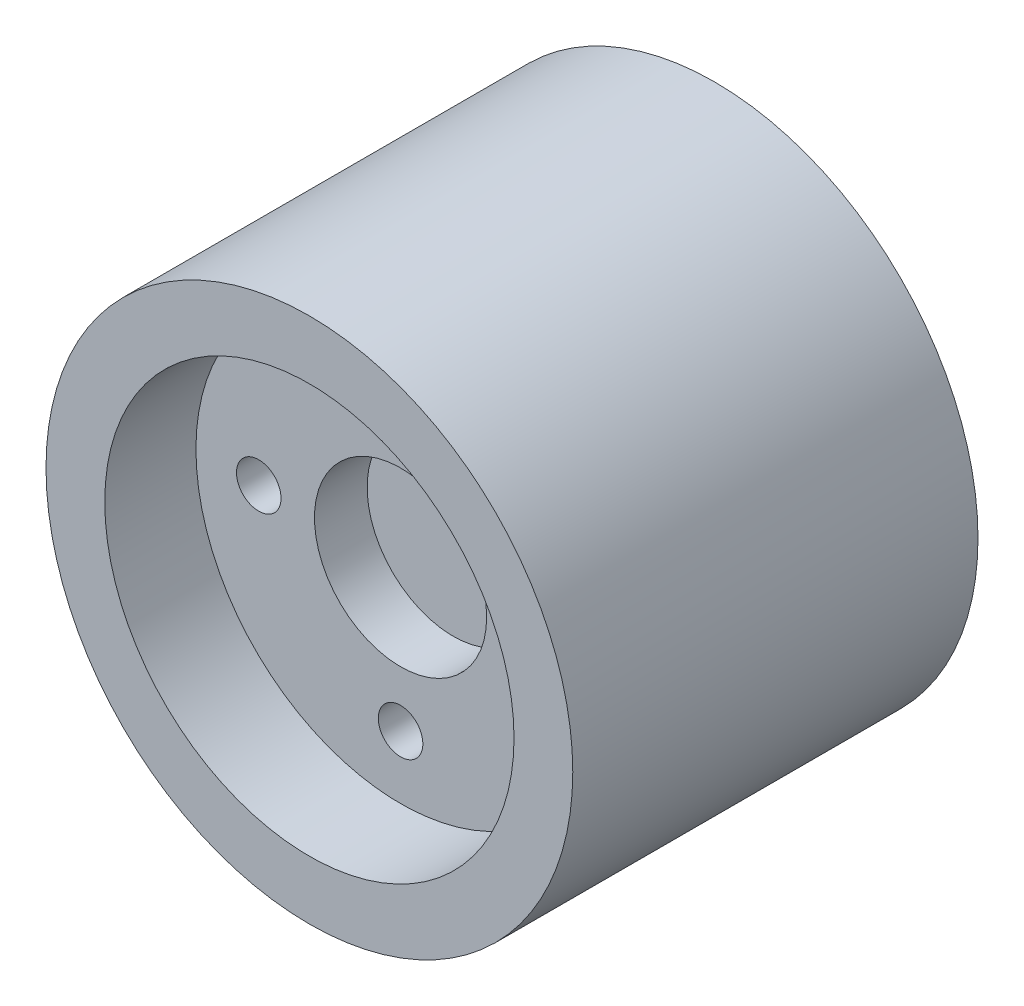
SolidWorks part; units mm, degrees
ref_plane "Front Plane" through (0, 0, 0) normal (0, 0, 1) x (1, 0, 0)
ref_plane "Top Plane" through (0, 0, 0) normal (0, 1, 0) x (1, 0, 0)
ref_plane "Right Plane" through (0, 0, 0) normal (1, 0, 0) x (0, 0, -1)
sketch "Sketch1" plane through (0, 0, 0) normal (0, 0, 1) x (1, 0, 0)
  circle A0 centre (0, 0) radius 13
  dimension "D1" = 26
extrude "Boss-Extrude1" add sketch "Sketch1" along normal blind 20
sketch "Sketch2" plane through (0, 0, 20) normal (0, 0, 1) x (1, 0, 0)
  circle A0 centre (0, 0) radius 10.1
  dimension "D1" = 20.2
extrude "Cut-Extrude1" cut sketch "Sketch2" against normal blind 4.5
sketch "Sketch3" plane through (0, 0, 15.5) normal (0, 0, 1) x (1, 0, 0)
  circle A0 centre (0, 0) radius 4.25
  dimension "D1" = 8.5
extrude "Cut-Extrude2" cut sketch "Sketch3" against normal blind 2.6
sketch "Sketch4" plane through (0, 0, 0) normal (0, 0, -1) x (-1, 0, 0)
  circle A0 centre (0, 0) radius 2.125
  dimension "D1" = 4.25
extrude "Cut-Extrude3" cut sketch "Sketch4" against normal blind 10
sketch "Sketch5" plane through (0, 0, 0) normal (0, 0, -1) x (-1, 0, 0)
  circle A0 centre (0, 7) radius 2
  circle A1 centre (7, 0) radius 2
  circle A2 centre (0, -7) radius 2
  circle A4 centre (-7, 0) radius 2 [skipped]
  circle A5 centre (0, 0) radius 2.125 construction
  point P11 (0, 0)
  dimension "D2" = 4
  dimension "D1" = 7
  dimension "D4" = 7
extrude "Cut-Extrude4" cut sketch "Sketch5" against normal offset from surface (13.5 mm away) 2 up to face at (4.25, 0, 15.5)
sketch "Sketch6" plane through (0, 0, 0) normal (0, 0, -1) x (-1, 0, 0)
  circle A0 centre (0, 7) radius 1.1
  circle A1 centre (7, 0) radius 1.1
  circle A2 centre (0, -7) radius 1.1
  circle A4 centre (-7, 0) radius 1.1 [skipped]
  circle A5 centre (0, 7) radius 2 construction
  point P12 (0, 0)
  dimension "D1" = 2.2
  dimension "D2" = 7
  dimension "D4" = 7
extrude "Cut-Extrude5" cut sketch "Sketch6" against normal through all
sketch "Sketch7" plane through (0, 0, 0) normal (0, 0, -1) x (-1, 0, 0)
  line L0 (0, 0) -> (-20.2439, 0) construction
  circle A0 centre (-6, 5) radius 2.1
  circle A1 centre (-6, -5) radius 2.1
  dimension "D3" = 4.2
  dimension "D1" = 5
  dimension "D2" = 6
extrude "Cut-Extrude6" cut sketch "Sketch7" against normal blind 6
equation "\"L1\"= 120mm'Upper arm"
equation "\"L3\"= 75mm'Wrist→TCP"
equation "\"h0\"= 75mm'Shoulder height"
equation "\"t_link\"= 3mm'Link plate thickness"
equation "\"t_bracket\"= 4mm'Bracket thickness"
equation "\"d_pin\"= 4mm'Pin diameter (M4)"
equation "\"c_fit\"= 0.2mm'Nominal clearance - measured PLA 2026-10-01"
equation "\"L2\"= 120mm'Forearm"
equation "\"c_fit_pivot\"= \"c_fit\" + 0.05mm'Gripper pivot clearance - chosen 0.25 mm 2026-10-01"
equation "\"d_pin_gripper\"= 3mm'Gripper pivot diameter"
equation "\"w_link\"= 20mm'Link plate depth (bending direction)"
equation "\"w_gap\"= 20mm'Twin-plate gap - provisional, set by elbow servo mount"
equation "\"d_boss\"= 13mm'MG996R output boss dia - from downloaded model, verify with calipers"
equation "\"c_boss\"= 1mm'Radial clearance around servo boss"
equation "\"d_servo_hole\"= \"d_boss\" + 2 * \"c_boss\"'Plate clearance hole for servo boss (15 mm)"
equation "\"t_rim\"= 9.5mm'Min material around servo hole (M3 hole + 3 mm webs each side)"
equation "\"w_link_end\"= \"d_servo_hole\" + 2 * \"t_rim\"'Link plate end width at servo end (34 mm)"
equation "\"d_hole_m3\"= \"d_pin_gripper\" + \"c_fit\"'M3 bolt clearance hole (spacer and adapter bolts)"
equation "\"d_hole_pivot\"= \"d_pin\" + \"c_fit_pivot\"'M4 pivot hole where the pin rotates (4.25 mm)"
equation "\"d_horn\"= 20mm'Horn disc diameter (circular horn) - from MG996R model"
equation "\"t_horn\"= 2.3mm'Horn disc thickness"
equation "\"g_horn\"= 2.2mm'Gap from horn disc to plate 2 inner face - from MockShoulder"
equation "\"d_horn_pocket\"= \"d_horn\" + \"c_fit\"'Adapter pocket for horn disc (20.2 mm)"
equation "\"h_horn_pocket\"= \"g_horn\" + \"t_horn\"'Pocket depth from adapter plate-2 face (4.5 mm)"
equation "\"d_horn_screw_cb\"= 8.5mm'Recess for horn centre-screw head (head is 7.5 mm)"
equation "\"h_horn_screw_cb\"= 2.6mm'Recess depth (head is 2.35 mm tall)"
equation "\"d_adapter\"= 26mm'Horn adapter outer diameter"
equation "\"h_adapter\"= \"w_gap\"'Adapter length, fills the plate gap"
equation "\"t_adapter_floor\"= 2mm'Floor under horn disc that the horn screws pass through"
equation "\"d_horn_screw_hole\"= 2.2mm'Clearance for M2 self-tapper through the floor"
equation "\"r_horn_screw\"= 7mm'Horn screw hole radius (14 mm square pattern)"
equation "\"d_access\"= 4mm'Access bore for the M2 screws from the plate-1 side"
equation "\"d_insert_m3\"= 4.2mm'Hole for M3 heat-set insert - check the insert maker spec"
equation "\"h_insert_m3\"= 6mm'Insert hole depth"
equation "\"x_adapter_bolt\"= 6mm'Adapter bolt offset from pin, along the arm toward its middle"
equation "\"y_adapter_bolt\"= 5mm'Adapter bolt offset from pin, across the arm (+/-)"
equation "\"d_csk_m3\"= 6.4mm'Countersink diameter in plate 1 for M3 flat head (90 deg)"
equation "\"h_pin_bore\"= 10mm'M4 pin engagement depth in the adapter"
equation "\"D1@Sketch1\"=\"d_adapter\""
equation "\"D1@Boss-Extrude1\"=\"w_gap\""
equation "\"D1@Sketch2\"=\"d_horn_pocket\""
equation "\"D1@Sketch3\"=\"d_horn_screw_cb\""
equation "\"D1@Cut-Extrude2\"=\"h_horn_screw_cb\""
equation "\"D1@Sketch4\"=\"d_hole_pivot\""
equation "\"D1@Cut-Extrude3\"=\"h_pin_bore\""
equation "\"D1@Sketch5\"=\"r_horn_screw\""
equation "\"D2@Sketch5\"=\"d_access\""
equation "\"D4@Sketch5\"=\"r_horn_screw\""
equation "\"D1@Cut-Extrude4\"=\"t_adapter_floor\""
equation "\"D1@Sketch6\"=\"d_horn_screw_hole\""
equation "\"D2@Sketch6\"=\"r_horn_screw\""
equation "\"D4@Sketch6\"=\"r_horn_screw\""
equation "\"D1@Sketch7\"=\"y_adapter_bolt\""
equation "\"D2@Sketch7\"=\"x_adapter_bolt\""
equation "\"D3@Sketch7\"=\"d_insert_m3\""
equation "\"D1@Cut-Extrude6\"=\"h_insert_m3\""
